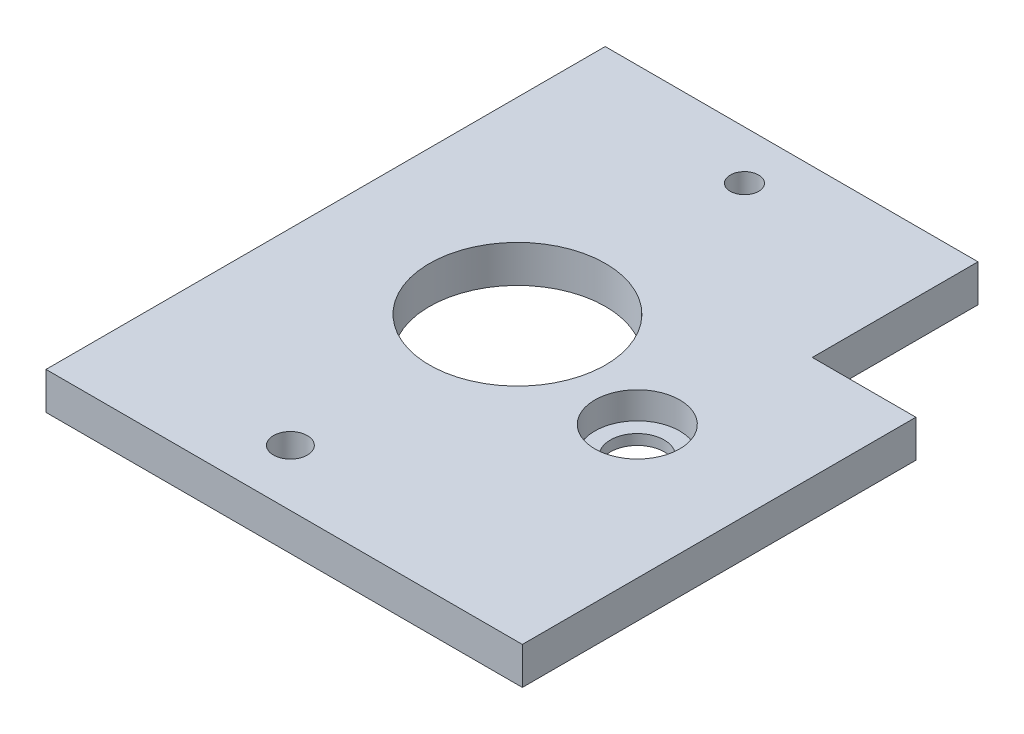
SolidWorks part; units mm, degrees
ref_plane "前视基准面" through (0, 0, 0) normal (0, 0, 1) x (1, 0, 0)
ref_plane "上视基准面" through (0, 0, 0) normal (0, 1, 0) x (1, 0, 0)
ref_plane "右视基准面" through (0, 0, 0) normal (1, 0, 0) x (0, 0, -1)
other "Configuration Table"
sketch "草图1" plane through (0, 0, 0) normal (0, 1, 0) x (1, 0, 0)
  line L1 (0, 0) -> (46, 0)
  line L2 (0, 0) -> (0, 54)
  line L3 (0, 54) -> (46, 54)
  line L4 (46, 0) -> (46, 54)
  dimension "D1" = 46
  dimension "D2" = 54
extrude "凸台-拉伸1" add sketch "草图1" along normal blind 3.6
sketch "草图2" plane through (0, 0, 0) normal (0, -1, 0) x (-1, 0, 0)
  line L0 (0, 54) -> (0, 0) construction
  line L1 (-46, 54) -> (0, 54) construction
  circle A0 centre (-18.15, 49.3) radius 1.3685
  circle A1 centre (-18.15, 5.45) radius 1.6344
  circle A2 centre (-18.15, 27.375) radius 8.5
  circle A3 centre (-33.15, 23.95) radius 4.1
  point P6 (0, 27)
  point P9 (-23, 54)
  dimension "D7" = 17
  dimension "D10" = 8.2
  dimension "D1" = 22.3
  dimension "D2" = 4.85
  dimension "D3" = 0
  dimension "D4" = 43.85
  dimension "D5" = 0
  dimension "D6" = 21.925
  dimension "D8" = 15
  dimension "D9" = 18.5
extrude "切除-拉伸1" cut sketch "草图2" against normal blind 3.6
sketch "草图4" plane through (0, 0, 0) normal (0, -1, 0) x (-1, 0, 0)
  circle A0 centre (-33.15, 23.95) radius 4.1
  circle A1 centre (-33.15, 23.95) radius 2.6
  dimension "D1" = 5.2
extrude "凸台-拉伸2" add sketch "草图4" against normal blind 1
sketch "草图5" plane through (0, 3.6, 0) normal (0, 1, 0) x (1, 0, 0)
  line L0 (46, 0) -> (46, 54) construction
  line L1 (46, 54) -> (36, 54)
  line L2 (46, 54) -> (46, 38)
  line L3 (46, 38) -> (36, 38)
  line L4 (36, 54) -> (36, 38)
  line L5 (46, 54) -> (0, 54) construction
  dimension "D1" = 16
  dimension "D2" = 10
extrude "切除-拉伸2" cut sketch "草图5" against normal blind 4
equation "\"D6@草图2\"=\"D4@草图2\"/2"
equation "\"D1@凸台-拉伸2\"=3.60-2.6"
